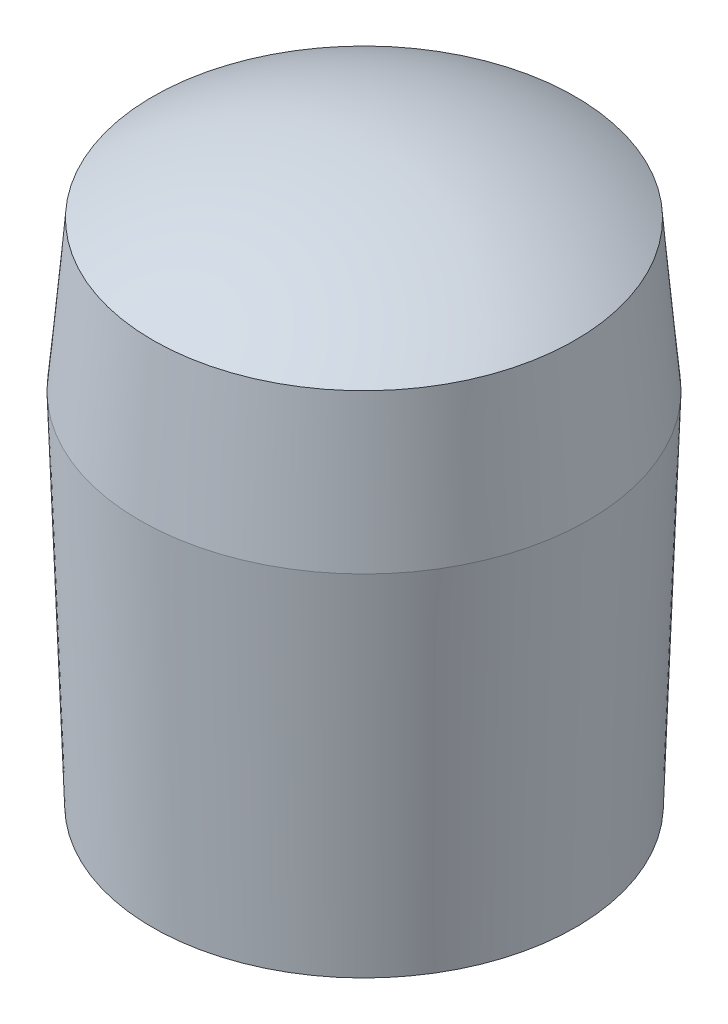
SolidWorks part; units mm, degrees
ref_plane "Front Plane" through (0, 0, 0) normal (0, 0, 1) x (1, 0, 0)
ref_plane "Top Plane" through (0, 0, 0) normal (0, 1, 0) x (1, 0, 0)
ref_plane "Right Plane" through (0, 0, 0) normal (1, 0, 0) x (0, 0, -1)
sketch "Sketch1" plane through (0, 0, 0) normal (0, 1, 0) x (1, 0, 0)
  circle A0 centre (0, 0) radius 0.75
  dimension "D1" = 1.5
extrude "Boss-Extrude1" add sketch "Sketch1" along normal blind 0.5 draft 5
dome "Dome1" faces to dome 1 distance 0.2 reverse direction no elliptical dome no face at (0, 0.5, 0.7063) parameters "D1"=0.2
sketch "Sketch2" plane through (0, 0, 0) normal (0, -1, 0) x (1, 0, 0)
  circle A0 centre (0, 0) radius 0.75
  dimension "D1" = 1.5
extrude "Boss-Extrude2" add sketch "Sketch2" along normal blind 1.2 draft 2
dome "Dome3" faces to dome 1 distance 0.2 reverse direction no elliptical dome no face at (0, -1.2, -0.7081) parameters "D1"=0.2
